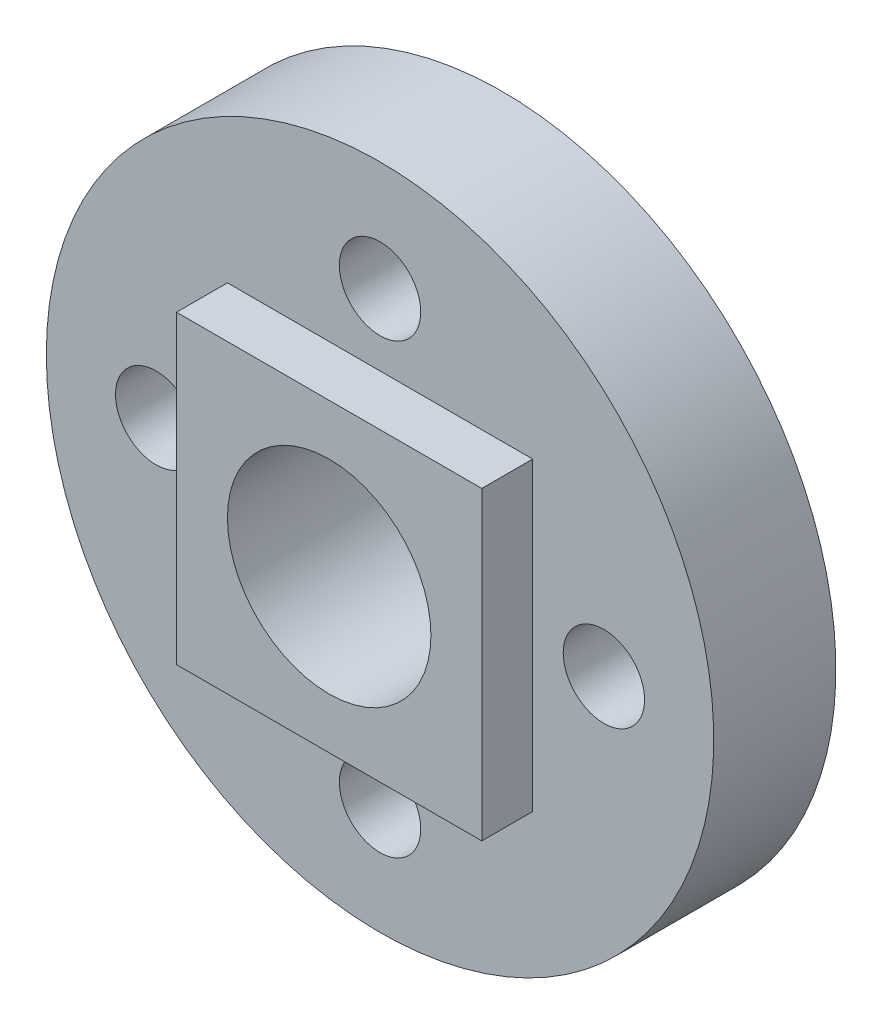
SolidWorks part; units mm, degrees
ref_plane "Front Plane" through (0, 0, 0) normal (0, 0, 1) x (1, 0, 0)
ref_plane "Top Plane" through (0, 0, 0) normal (0, 1, 0) x (1, 0, 0)
ref_plane "Right Plane" through (0, 0, 0) normal (1, 0, 0) x (0, 0, -1)
sketch "Model" plane through (0, 0, 0) normal (0, 0, 1) x (1, 0, 0)
  line L0 (9.525, 9.525) -> (9.525, -9.525)
  line L1 (-9.525, 9.525) -> (9.525, 9.525)
  line L2 (-9.525, -9.525) -> (-9.525, 9.525)
  line L3 (9.525, -9.525) -> (-9.525, -9.525)
  circle A0 centre (0, 13.97) radius 2.54
  circle A1 centre (-13.97, 0) radius 2.54
  circle A2 centre (0, -13.97) radius 2.54
  circle A3 centre (13.97, 0) radius 2.54
  circle A4 centre (0, 0) radius 20.828
  circle A5 centre (0, 0) radius 6.35
  text T0 "SOLIDWORKS Educational Product." font "Century Gothic" height 4.8336
  text T1 "For Instructional Use Only." font "TXT" height 4.8336
sketch "Sketch2" plane through (0, 0, 0) normal (0, 0, 1) x (1, 0, 0)
  circle A0 centre (0, -13.97) radius 2.54 construction
  circle A1 centre (-13.97, 0) radius 2.54 construction
  circle A2 centre (0, 13.97) radius 2.54 construction
  circle A3 centre (13.97, 0) radius 2.54 construction
  circle A4 centre (0, 0) radius 20.828 construction
  circle A5 centre (0, 0) radius 6.35 construction
  circle A6 centre (0, -13.97) radius 2.54
  circle A7 centre (-13.97, 0) radius 2.54
  circle A8 centre (0, 13.97) radius 2.54
  circle A9 centre (13.97, 0) radius 2.54
  circle A10 centre (0, 0) radius 20.828
  circle A11 centre (0, 0) radius 6.35
extrude "Boss-Extrude1" add sketch "Sketch2" along normal blind 7.62
sketch "Sketch3" plane through (0, 0, 7.62) normal (0, 0, 1) x (1, 0, 0)
  line L0 (-9.525, -9.525) -> (-9.525, 9.525) construction
  line L1 (9.525, -9.525) -> (-9.525, -9.525) construction
  line L2 (9.525, 9.525) -> (9.525, -9.525) construction
  line L3 (-9.525, 9.525) -> (9.525, 9.525) construction
  line L4 (-9.525, -9.525) -> (-9.525, 9.525)
  line L5 (9.525, -9.525) -> (-9.525, -9.525)
  line L6 (9.525, 9.525) -> (9.525, -9.525)
  line L7 (-9.525, 9.525) -> (9.525, 9.525)
  circle A0 centre (0, 0) radius 6.35 construction
  circle A1 centre (0, 0) radius 6.35
extrude "Boss-Extrude2" add sketch "Sketch3" along normal blind 3.175
